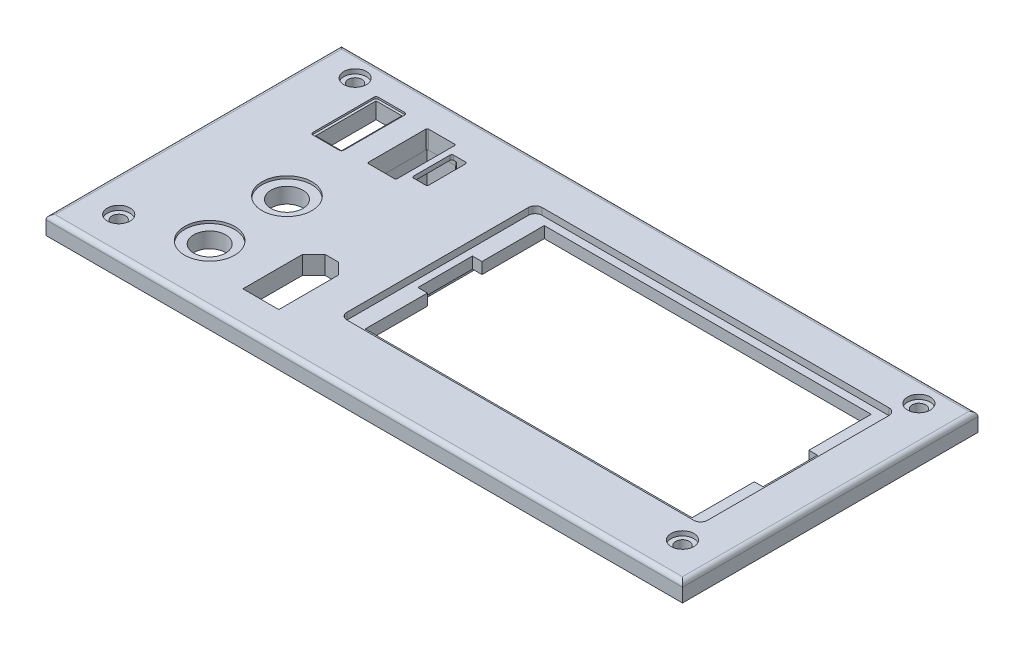
SolidWorks part; units mm, degrees
ref_plane "Спереди" through (0, 0, 0) normal (0, 0, 1) x (1, 0, 0)
ref_plane "Сверху" through (0, 0, 0) normal (0, 1, 0) x (1, 0, 0)
ref_plane "Справа" through (0, 0, 0) normal (1, 0, 0) x (0, 0, -1)
sketch "Эскиз1" plane through (0, 0, 0) normal (0, 1, 0) x (1, 0, 0)
  line L1 (-60, 30) -> (80, 30)
  line L2 (-60, 30) -> (-60, -35)
  line L3 (-60, -35) -> (80, -35)
  line L4 (80, 30) -> (80, -35)
  line L5 (-60, 30) -> (80, -35) construction
  line L6 (-60, -35) -> (80, 30) construction
  point P0 (0, 0)
  dimension "D1" = 65
  dimension "D2" = 140
extrude "Передняя панель основа" add sketch "Эскиз1" along normal blind 4
sketch "Эскиз2" plane through (0, 4, 0) normal (0, 1, 0) x (1, 0, 0)
  line L1 (71, 20.9) -> (-8.3, 20.9)
  line L2 (71, 20.9) -> (71, -22)
  line L3 (71, -22) -> (-8.3, -22)
  line L4 (-8.3, 20.9) -> (-8.3, -22)
  line L5 (71, 20.9) -> (-8.3, -22) construction
  line L6 (71, -22) -> (-8.3, 20.9) construction
  point P0 (31.35, -0.55)
  dimension "D1" = 42.9
  dimension "D2" = 79.3
  dimension "D3" = 13
  dimension "D4" = 9
extrude "Внешняя рамка модуля" cut sketch "Эскиз2" against normal blind 1.5
fillet "Уголки скругления рамки выреза модуля" radius 1.5 4 edges at (71, 3.25, 22) (-8.3, 3.25, 22) (71, 3.25, -20.9) (-8.3, 3.25, -20.9)
sketch "Эскиз3" plane through (0, 2.5, 0) normal (0, 1, 0) x (1, 0, 0)
  line L0 (-60, -35) -> (80, -35) construction
  line L1 (-4.6, 19.2) -> (67.3, 19.2)
  line L2 (-4.6, 19.2) -> (-4.6, -20.2)
  line L3 (-4.6, -20.2) -> (67.3, -20.2)
  line L4 (67.3, 19.2) -> (67.3, -20.2)
  line L5 (-4.6, 19.2) -> (67.3, -20.2) construction
  line L6 (-4.6, -20.2) -> (67.3, 19.2) construction
  line L7 (69.5, 20.9) -> (-6.8, 20.9) construction
  line L8 (-6.8, -22) -> (69.5, -22) construction
  line L9 (71, -20.5) -> (71, 19.4) construction
  line L10 (-8.3, 19.4) -> (-8.3, -20.5) construction
  point P0 (31.35, -0.5)
  dimension "D1" = 39.4
  dimension "D2" = 71.9
  dimension "D3" = 14.8
  dimension "D4" = 12.7
  dimension "D5" = 1.7
  dimension "D6" = 1.8
  dimension "D7" = 3.7
  dimension "D8" = 3.7
extrude "Вырез тела модуля" cut sketch "Эскиз3" against normal blind 3
sketch "Эскиз4" plane through (0, 2.5, 0) normal (0, 1, 0) x (1, 0, 0)
  line L0 (-4.6, 19.2) -> (-4.6, -20.2) construction
  line L1 (-2.5, -6.5) -> (-6.7, -6.5)
  line L2 (-2.5, -6.5) -> (-2.5, 5.5)
  line L3 (-2.5, 5.5) -> (-6.7, 5.5)
  line L4 (-6.7, -6.5) -> (-6.7, 5.5)
  line L5 (-2.5, -6.5) -> (-6.7, 5.5) construction
  line L6 (-2.5, 5.5) -> (-6.7, -6.5) construction
  line L7 (69.2, -6.5) -> (69.2, 5.5)
  line L8 (69.2, -6.5) -> (65, -6.5)
  line L9 (65, -6.5) -> (65, 5.5)
  line L10 (69.2, 5.5) -> (65, 5.5)
  point P0 (-4.6, -0.5)
  dimension "D1" = 12
  dimension "D2" = 4.2
  dimension "D3" = 2
extrude "Ушки модуля" cut sketch "Эскиз4" against normal blind 3
sketch "Эскиз5" plane through (0, 4, 0) normal (0, 1, 0) x (1, 0, 0)
  line L1 (-60, -35) -> (80, -35) construction
  line L2 (-60, 30) -> (-60, -35) construction
  circle A0 centre (-37, -5) radius 5.5
  circle A1 centre (-37, -22) radius 5.5
  dimension "D1" = 11
  dimension "D2" = 11
  dimension "D3" = 13
  dimension "D4" = 23
  dimension "D5" = 17
extrude "Внешние кольца под бананы" cut sketch "Эскиз5" against normal blind 0.6
sketch "Эскиз6" plane through (0, 3.4, 0) normal (0, 1, 0) x (1, 0, 0)
  circle A0 centre (-37, -5) radius 3.5
  circle A1 centre (-37, -22) radius 3.5
  dimension "D1" = 7
  dimension "D2" = 7
extrude "Вырез под бананы" cut sketch "Эскиз6" against normal through all
sketch "Эскиз7" plane through (0, 4, 0) normal (0, 1, 0) x (1, 0, 0)
  line L1 (-46.3, 23.9) -> (-39.5, 23.9)
  line L2 (-46.3, 23.9) -> (-46.3, 9.5)
  line L3 (-46.3, 9.5) -> (-39.5, 9.5)
  line L4 (-39.5, 23.9) -> (-39.5, 9.5)
  line L5 (-46.3, 23.9) -> (-39.5, 9.5) construction
  line L6 (-46.3, 9.5) -> (-39.5, 23.9) construction
  line L10 (-8.3, 19.4) -> (-8.3, -20.5) construction
  line L11 (69.5, 20.9) -> (-6.8, 20.9) construction
  circle A0 centre (-37, -5) radius 5.5 construction
  point P0 (-42.9, 16.7)
  dimension "D1" = 14.4
  dimension "D2" = 6.8
  dimension "D4" = 2.5
extrude "Внешняя рамка USB" cut sketch "Эскиз7" against normal blind 0.4
sketch "Эскиз8" plane through (0, 3.6, 0) normal (0, 1, 0) x (1, 0, 0)
  line L0 (-39.5, 23.9) -> (-46.3, 23.9) construction
  line L1 (-45.75, 23.35) -> (-40.05, 23.35)
  line L2 (-45.75, 23.35) -> (-45.75, 10.05)
  line L3 (-45.75, 10.05) -> (-40.05, 10.05)
  line L4 (-40.05, 23.35) -> (-40.05, 10.05)
  line L5 (-45.75, 23.35) -> (-40.05, 10.05) construction
  line L6 (-45.75, 10.05) -> (-40.05, 23.35) construction
  line L7 (-46.3, 9.5) -> (-39.5, 9.5) construction
  line L8 (-46.3, 23.9) -> (-46.3, 9.5) construction
  line L9 (-39.5, 9.5) -> (-39.5, 23.9) construction
  point P0 (-42.9, 16.7)
  dimension "D1" = 13.3
  dimension "D2" = 5.7
  dimension "D3" = 0.55
  dimension "D4" = 0.55
  dimension "D5" = 0.55
  dimension "D6" = 0.55
extrude "USB" cut sketch "Эскиз8" against normal through all
fillet "Скругление уголков 1 USB" radius 0.5 4 edges at (-46.3, 3.8, -9.5) (-39.5, 3.8, -9.5) (-39.5, 3.8, -23.9) (-46.3, 3.8, -23.9)
sketch "Эскиз9" plane through (0, 4, 0) normal (0, 1, 0) x (1, 0, 0)
  line L0 (-24.2, -27.5) -> (-16.3, -27.5)
  line L1 (-16.3, -27.5) -> (-16.3, -14.4)
  line L2 (-16.3, -14.4) -> (-18.8, -11.9)
  line L3 (-18.8, -11.9) -> (-21.7, -11.9)
  line L4 (-21.7, -11.9) -> (-24.2, -14.4)
  line L5 (-24.2, -14.4) -> (-24.2, -27.5)
  line L6 (-46.3, 23.4) -> (-46.3, 10) construction
  line L7 (-60, -35) -> (80, -35) construction
  line L8 (-8.3, 19.4) -> (-8.3, -20.5) construction
  line L9 (-60, 30) -> (-60, -35) construction
  circle A3 centre (-37, -22) radius 5.5 construction
  point P8 (-20.25, -27.5)
  point P9 (-20.25, -11.9)
  dimension "D4" = 7.5
  dimension "D1" = 7.9
  dimension "D2" = 15.6
  dimension "D3" = 2.5
  dimension "D5" = 8
  dimension "D6" = 12.8
  dimension "D7" = 35.8
extrude "XT60 на передней панели" cut sketch "Эскиз9" against normal through all
sketch "Эскиз10" plane through (0, 4, 0) normal (0, 1, 0) x (1, 0, 0)
  line L0 (80, 30) -> (-60, 30) construction
  line L1 (-60, 30) -> (-60, -35) construction
  line L2 (80, -35) -> (80, 30) construction
  line L3 (-60, -35) -> (80, -35) construction
  circle A0 centre (-52, 25) radius 1.5
  circle A1 centre (72, 25) radius 1.5
  circle A2 centre (72, -27) radius 1.5
  circle A3 centre (-52, -27) radius 1.5
  dimension "D1" = 3
  dimension "D2" = 5
  dimension "D3" = 8
  dimension "D5" = 8
  dimension "D6" = 5
  dimension "D7" = 8
  dimension "D8" = 8
  dimension "D9" = 8
  dimension "D10" = 8
  dimension "D4" = 2
extrude "Отверстия крепления передней панели к корпусу" cut sketch "Эскиз10" against normal through all
sketch "Эскиз13" plane through (0, 4, 0) normal (0, 1, 0) x (1, 0, 0)
  circle A0 centre (-52, 25) radius 2.5
  circle A1 centre (72, 25) radius 2.5
  circle A2 centre (72, -27) radius 2.5
  circle A3 centre (-52, -27) radius 2.5
  dimension "D1" = 5
  dimension "D2" = 2
extrude "Фаска под головку болта передней панели" cut sketch "Эскиз13" against normal blind 1
fillet "Скругление1" radius 1 4 edges at (10, 4, 35) (80, 4, 2.5) (-60, 4, 2.5) (10, 4, -30)
sketch "Эскиз14" plane through (0, 4, 0) normal (0, 1, 0) x (1, 0, 0)
  line L0 (-28.2, 10.15) -> (-34.5, 10.15)
  line L1 (-34.5, 10.15) -> (-34.5, 23.35)
  line L2 (-34.5, 23.35) -> (-28.2, 23.35)
  line L3 (-28.2, 23.35) -> (-28.2, 25.9)
  line L4 (-28.2, 25.9) -> (-26.9, 25.9)
  line L5 (-26.9, 25.9) -> (-26.9, 21.15)
  line L6 (-26.9, 21.15) -> (-23.5, 21.15)
  line L7 (-23.5, 21.15) -> (-23.5, 12.35)
  line L8 (-23.5, 12.35) -> (-26.9, 12.35)
  line L9 (-26.9, 12.35) -> (-26.9, 7.6)
  line L10 (-26.9, 7.6) -> (-28.2, 7.6)
  line L11 (-28.2, 7.6) -> (-28.2, 10.15)
  line L12 (-40.05, 23.35) -> (-45.75, 23.35) construction
  circle A0 centre (-37, -5) radius 3.5 construction
  dimension "D1" = 13.2
  dimension "D2" = 11
  dimension "D3" = 6.3
  dimension "D4" = 1.3
  dimension "D5" = 3.4
  dimension "D6" = 8.8
  dimension "D7" = 18.3
  dimension "D8" = 2.5
extrude "Вырез-Вытянуть1" cut sketch "Эскиз14" against normal through all
fillet "Скругление2" radius 0.4 2 edges at (-23.5, 2, -12.35) (-23.5, 2, -21.15)
fillet "Скругление3" radius 0.3 2 edges at (-34.5, 2, -10.15) (-34.5, 2, -23.35)
sketch "Эскиз15" plane through (0, 4, 0) normal (0, 1, 0) x (1, 0, 0)
  line L1 (-28.2, 26) -> (-26.9, 26)
  line L2 (-28.2, 26) -> (-28.2, 7.6)
  line L3 (-28.2, 7.6) -> (-26.9, 7.6)
  line L4 (-26.9, 26) -> (-26.9, 7.6)
  line L5 (-28.2, 26) -> (-26.9, 7.6) construction
  line L6 (-28.2, 7.6) -> (-26.9, 26) construction
  line L11 (-26.9, 25.9) -> (-28.2, 25.9) construction
  line L12 (-28.2, 7.6) -> (-26.9, 7.6) construction
  line L15 (-28.2, 25.9) -> (-28.2, 23.35) construction
  point P0 (-27.55, 16.8)
  point P10 (-27.55, 7.6)
  dimension "D1" = 18.4
extrude "Бобышка-Вытянуть1" add sketch "Эскиз15" against normal blind 1
fillet "Скругление4" radius 0.3 2 edges at (-28.2, 3.5, -10.15) (-28.2, 3.5, -23.35)
fillet "Скругление5" radius 0.4 2 edges at (-26.9, 3.5, -12.35) (-26.9, 3.5, -21.15)
sketch "Эскиз17" plane through (0, 0, 0) normal (0, -1, 0) x (1, 0, 0)
  line L0 (-34.6184, -9.9961) -> (-28.3093, -9.9961)
  line L1 (-28.3093, -9.9961) -> (-28.3093, -7.5533)
  line L2 (-28.3093, -7.5533) -> (-25.8093, -7.5533)
  line L3 (-25.8093, -7.5533) -> (-25.8093, -12.1697)
  line L4 (-25.8093, -12.1697) -> (-23.3093, -12.1697)
  line L5 (-23.3093, -12.1697) -> (-23.3093, -21.2455)
  line L6 (-23.3093, -21.2455) -> (-25.8093, -21.2455)
  line L7 (-25.8093, -21.2455) -> (-25.8093, -25.9546)
  line L8 (-25.8093, -25.9546) -> (-28.3093, -25.9546)
  line L9 (-28.3093, -25.9546) -> (-28.3093, -23.4086)
  line L10 (-28.3093, -23.4086) -> (-34.6184, -23.4086)
  line L11 (-34.6184, -23.4086) -> (-34.6184, -9.9961)
  point P2 (0, 0)
extrude "Вытянуть-Тонкостенный1" add sketch "Эскиз17" along normal blind 15 thin thin type one direction wall 2
fillet "Скругление6" radius 0.5 12 edges at (-23.8093, -7.5, -23.2455) (-23.8093, -7.5, -27.9546) (-30.3093, -7.5, -27.9546) (-30.3093, -7.5, -25.4086) (-36.6184, -7.5, -25.4086) (-36.6184, -7.5, -7.9961) (-30.3093, -7.5, -7.9961) (-30.3093, -7.5, -5.5533) (-21.3093, -7.5, -23.2455) (-23.8093, -7.5, -10.1697) (-21.3093, -7.5, -10.1697) (-23.8093, -7.5, -5.5533)
sketch "Эскиз18" plane through (0, 0, 0) normal (0, -1, 0) x (1, 0, 0)
  line L1 (-25.8093, -7.5533) -> (-26.9, -7.5533)
  line L2 (-25.8093, -7.5533) -> (-25.8093, -25.9)
  line L3 (-25.8093, -25.9) -> (-26.9, -25.9)
  line L4 (-26.9, -7.5533) -> (-26.9, -25.9)
extrude "Вырез-Вытянуть2" cut sketch "Эскиз18" against normal blind 3
